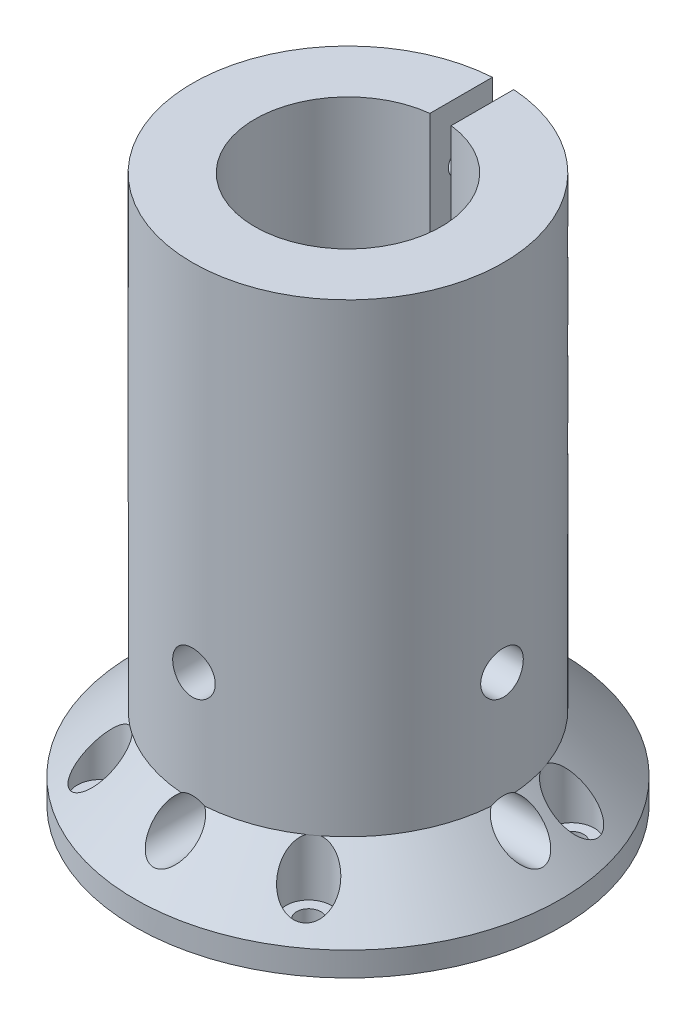
SolidWorks part; units mm, degrees
ref_plane "Front Plane" through (0, 0, 0) normal (0, 0, 1) x (1, 0, 0)
ref_plane "Top Plane" through (0, 0, 0) normal (0, 1, 0) x (1, 0, 0)
ref_plane "Right Plane" through (0, 0, 0) normal (1, 0, 0) x (0, 0, -1)
sketch "Sketch1" plane through (0, 0, 0) normal (0, 1, 0) x (1, 0, 0)
  circle A0 centre (0, 0) radius 25 construction
  circle A1 centre (0, 25) radius 1.7
  circle A2 centre (23.7764, 7.7254) radius 1.7
  circle A3 centre (14.6946, -20.2254) radius 1.7
  circle A4 centre (-14.6946, -20.2254) radius 1.7
  circle A5 centre (-23.7764, 7.7254) radius 1.7
  circle A6 centre (0, 0) radius 30
  circle A7 centre (0, 0) radius 17.5
  point P16 (0, 0)
  dimension "D1" = 50
  dimension "D2" = 3.4
  dimension "D4" = 60
  dimension "D5" = 35
  dimension "D3" = 5
extrude "Boss-Extrude1" add sketch "Sketch1" along normal blind 3
sketch "Sketch2" plane through (0, 3, 0) normal (0, 1, 0) x (1, 0, 0)
  circle A0 centre (0, 25) radius 3.1 construction
  circle A1 centre (0, 0) radius 21.9
  circle A2 centre (0, 0) radius 17.5 construction
  circle A3 centre (0, 0) radius 17.5
  dimension "D1" = 6.2
extrude "Boss-Extrude2" add sketch "Sketch2" along normal blind 32 from surface starting at face at (0, 0, 30)
chamfer "Chamfer1" distance 8.5 angle 45 1 edges at (0, 3, 21.9)
ref_plane "Plane1" through (0, 11.5, 0) normal (0, -1, 0) x (-1, 0, 0)
sketch "Sketch3" plane through (0, 11.5, 0) normal (0, -1, 0) x (-1, 0, 0)
  circle A0 centre (0, 25) radius 1.7 construction
  circle A1 centre (0, 25) radius 1.7
  circle A2 centre (0, 25) radius 3.2
  circle A3 centre (23.7764, 7.7254) radius 3.2
  circle A4 centre (14.6946, -20.2254) radius 3.2
  circle A5 centre (-14.6946, -20.2254) radius 3.2
  circle A6 centre (-23.7764, 7.7254) radius 3.2
  circle A7 centre (-23.7764, 7.7254) radius 1.7 construction
  circle A8 centre (-14.6946, -20.2254) radius 1.7 construction
  circle A9 centre (14.6946, -20.2254) radius 1.7 construction
  circle A10 centre (23.7764, 7.7254) radius 1.7 construction
  circle A11 centre (-23.7764, 7.7254) radius 1.7
  circle A12 centre (-14.6946, -20.2254) radius 1.7
  circle A13 centre (14.6946, -20.2254) radius 1.7
  circle A14 centre (23.7764, 7.7254) radius 1.7
  point P15 (0, 0)
  dimension "D2" = 5
  dimension "D1" = 1.5
extrude "Cut-Extrude3" cut sketch "Sketch3" along normal blind 8
sketch "Sketch4" plane through (0, 0, 0) normal (0, 0, 1) x (1, 0, 0)
  line L0 (0, 9) -> (0, 0) construction
  line L1 (0, 0) -> (0, 27) construction
  circle A0 centre (0, 9) radius 3
  circle A1 centre (0, 27) radius 3
  dimension "D1" = 6
  dimension "D3" = 27
  dimension "D2" = 9
extrude "Cut-Extrude4" cut sketch "Sketch4" along normal through all
sketch "Sketch14" plane through (0, 0, 0) normal (1, 0, 0) x (0, 0, -1)
  line L0 (0, 9) -> (0, 27) construction
  line L1 (0, 9) -> (0, 0) construction
  circle A0 centre (0, 27) radius 3
  circle A1 centre (0, 9) radius 3
  point P0 (0, 8.2565)
  dimension "D1" = 6
  dimension "D2" = 9
  dimension "D3" = 27
extrude "Cut-Extrude11" cut sketch "Sketch14" against normal through all both and the other way through all
sketch "Sketch5" plane through (0, 32, 0) normal (0, 1, 0) x (1, 0, 0)
  circle A0 centre (0, 0) radius 13.125
  circle A1 centre (0, 0) radius 21.9 construction
  circle A2 centre (0, 0) radius 21.9
  dimension "D1" = 26.25
extrude "Boss-Extrude3" add sketch "Sketch5" along normal blind 45
chamfer "Chamfer2" distance 4.5 angle 45 1 edges at (0, 32, 17.5)
sketch "Sketch6" plane through (0, 77, 0) normal (0, 1, 0) x (1, 0, 0)
  line L0 (0, 13.125) -> (0, 0) construction
  line L1 (-1.5, 4.35) -> (1.5, 4.35)
  line L2 (-1.5, 4.35) -> (-1.5, 21.9)
  line L3 (-1.5, 21.9) -> (1.5, 21.9)
  line L4 (1.5, 4.35) -> (1.5, 21.9)
  line L5 (-1.5, 4.35) -> (1.5, 21.9) construction
  line L6 (-1.5, 21.9) -> (1.5, 4.35) construction
  circle A0 centre (0, 0) radius 13.125 construction
  circle A1 centre (0, 0) radius 21.9 construction
  point P0 (0, 13.125)
  dimension "D1" = 3
extrude "Cut-Extrude5" cut sketch "Sketch6" against normal blind 40
sketch "Sketch8" plane through (-1.5, 0, 0) normal (1, 0, 0) x (0, 0, -1)
  line L0 (17.4438, 77) -> (17.4438, 37) construction
  line L4 (21.8486, 77) -> (13.039, 77)
  line L5 (13.039, 77) -> (13.039, 37)
  line L6 (13.039, 37) -> (21.8486, 37)
  line L7 (21.8486, 37) -> (21.8486, 77)
  line L8 (21.8486, 77) -> (13.039, 77) construction
  line L9 (13.039, 77) -> (13.039, 37) construction
  line L10 (13.039, 37) -> (21.8486, 37) construction
  line L11 (21.8486, 37) -> (21.8486, 77) construction
  circle A0 centre (17.4438, 57) radius 1.8
  circle A1 centre (17.4438, 69) radius 1.8
  circle A2 centre (17.4438, 45) radius 1.8
  dimension "D2" = 3.6
  dimension "D3" = 12
  dimension "D4" = 12
  dimension "D1" = 0
extrude "Cut-Extrude6" cut sketch "Sketch8" against normal through all
sketch "Sketch9" plane through (-1.5, 0, 0) normal (1, 0, 0) x (0, 0, -1)
  line L1 (17.4465, 65.7091) -> (20.2951, 67.3569)
  line L2 (20.2951, 67.3569) -> (20.2924, 70.6478)
  line L3 (20.2924, 70.6478) -> (17.4411, 72.2909)
  line L4 (17.4411, 72.2909) -> (14.5924, 70.6431)
  line L5 (14.5924, 70.6431) -> (14.5951, 67.3522)
  line L6 (14.5951, 67.3522) -> (17.4465, 65.7091)
  line L7 (17.4437, 53.7091) -> (20.2938, 55.3545)
  line L8 (20.2938, 55.3545) -> (20.2938, 58.6454)
  line L9 (20.2938, 58.6454) -> (17.4438, 60.2909)
  line L10 (17.4438, 60.2909) -> (14.5938, 58.6455)
  line L11 (14.5938, 58.6455) -> (14.5938, 55.3546)
  line L12 (14.5938, 55.3546) -> (17.4437, 53.7091)
  line L13 (17.4048, 41.7093) -> (20.2741, 43.3209)
  line L14 (20.2741, 43.3209) -> (20.3131, 46.6116)
  line L15 (20.3131, 46.6116) -> (17.4827, 48.2907)
  line L16 (17.4827, 48.2907) -> (14.6135, 46.6791)
  line L17 (14.6135, 46.6791) -> (14.5745, 43.3884)
  line L18 (14.5745, 43.3884) -> (17.4048, 41.7093)
  circle A0 centre (17.4438, 45) radius 1.8 construction
  circle A1 centre (17.4438, 57) radius 1.8 construction
  circle A2 centre (17.4438, 69) radius 1.8 construction
  circle A3 centre (17.4438, 69) radius 2.85 construction
  circle A4 centre (17.4438, 57) radius 2.85 construction
  circle A5 centre (17.4438, 45) radius 2.85 construction
  circle A21 centre (17.4438, 45) radius 1.8 construction
  circle A22 centre (17.4438, 57) radius 1.8 construction
  circle A23 centre (17.4438, 69) radius 1.8 construction
  circle A24 centre (17.4438, 45) radius 2.8 construction
  circle A25 centre (17.4438, 57) radius 2.8 construction
  circle A26 centre (17.4438, 69) radius 2.8 construction
  dimension "D2" = 5.7
  dimension "D1" = 1
extrude "Cut-Extrude7" cut sketch "Sketch9" against normal through all from offset 3 offset against normal yes
sketch "Sketch12" plane through (0, 0.012, -14.6501) normal (0, 0.0008, -1) x (-1, 0, 0)
  line L0 (16.3313, 60.2766) -> (8.239, 60.2766)
  line L1 (16.3313, 72.2766) -> (8.239, 72.2766)
  line L2 (16.3313, 72.2766) -> (16.3313, 65.6948)
  line L3 (16.3313, 65.6948) -> (8.239, 65.6948)
  line L4 (8.239, 72.2766) -> (8.239, 65.6948)
  line L5 (8.239, 60.2766) -> (8.239, 53.6948)
  line L6 (8.2291, 67.3403) -> (8.2357, 70.6312) construction
  line L7 (16.3301, 70.6312) -> (16.3276, 67.3403) construction
  line L8 (16.3313, 53.6948) -> (8.239, 53.6948)
  line L9 (16.3313, 60.2766) -> (16.3313, 53.6948)
  line L10 (16.3313, 48.2766) -> (8.239, 48.2766)
  line L11 (8.239, 48.2766) -> (8.239, 41.6948)
  line L12 (16.3313, 41.6948) -> (8.239, 41.6948)
  line L13 (16.3313, 48.2766) -> (16.3313, 41.6948)
  dimension "D1" = 3
sketch "Sketch10" plane through (1.5, 0, 0) normal (-1, 0, 0) x (0, 0, 1)
  circle A9 centre (-17.4438, 45) radius 1.8 construction
  circle A10 centre (-17.4438, 57) radius 1.8 construction
  circle A11 centre (-17.4438, 69) radius 1.8 construction
  circle A12 centre (-17.4438, 45) radius 1.8
  circle A13 centre (-17.4438, 57) radius 1.8
  circle A14 centre (-17.4438, 69) radius 1.8
extrude "Cut-Extrude8" cut sketch "Sketch10" against normal through all
sketch "Sketch11" plane through (1.5, 0, 0) normal (-1, 0, 0) x (0, 0, 1)
  circle A0 centre (-17.4438, 45) radius 1.4 construction
  circle A1 centre (-17.4438, 57) radius 1.4 construction
  circle A2 centre (-17.4438, 69) radius 1.4 construction
  circle A3 centre (-17.4438, 45) radius 1.4 construction
  circle A4 centre (-17.4438, 57) radius 1.4 construction
  circle A5 centre (-17.4438, 69) radius 1.4 construction
  circle A6 centre (-17.4438, 45) radius 3.1
  circle A7 centre (-17.4438, 57) radius 3.1
  circle A8 centre (-17.4438, 69) radius 3.1
  dimension "D1" = 1.7
extrude "Cut-Extrude9" cut sketch "Sketch11" along normal blind 17 from offset 20 offset against normal yes
